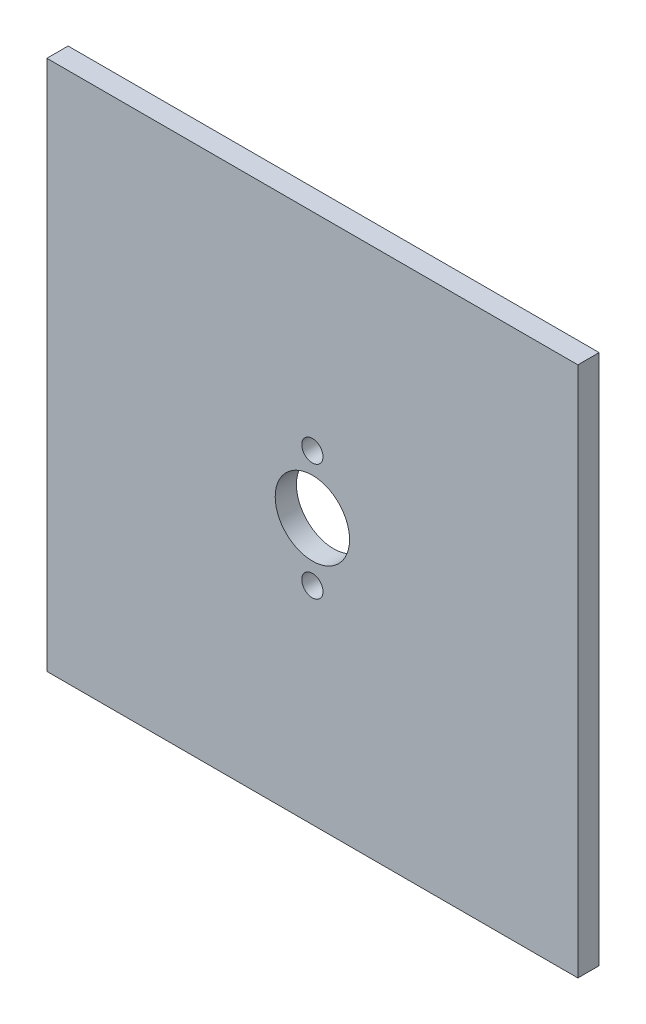
SolidWorks part; units mm, degrees
ref_plane "Front Plane" through (0, 0, 0) normal (0, 0, 1) x (1, 0, 0)
ref_plane "Top Plane" through (0, 0, 0) normal (0, 1, 0) x (1, 0, 0)
ref_plane "Right Plane" through (0, 0, 0) normal (1, 0, 0) x (0, 0, -1)
sketch "Sketch4" plane through (0, 0, 0) normal (0, 0, 1) x (1, 0, 0)
  line L1 (0, 0) -> (-50, 0)
  line L2 (0, 0) -> (0, 50)
  line L3 (0, 50) -> (-50, 50)
  line L4 (-50, 0) -> (-50, 50)
  dimension "D1" = 50
  dimension "D2" = 50
extrude "Boss-Extrude2" add sketch "Sketch4" along normal blind 2
sketch "Sketch5" plane through (0, 0, 2) normal (0, 0, 1) x (1, 0, 0)
  line L0 (-25, 50) -> (-25, 0) construction
  line L1 (0, 50) -> (-50, 50) construction
  line L2 (-50, 0) -> (0, 0) construction
  line L3 (-50, 25) -> (0, 25) construction
  line L4 (-50, 50) -> (-50, 0) construction
  line L5 (0, 0) -> (0, 50) construction
  circle A0 centre (-25, 30.5) radius 1
  circle A1 centre (-25, 19.5) radius 1
  dimension "D1" = 2
  dimension "D2" = 2
  dimension "D3" = 11
  dimension "D4" = 5.5
extrude "Cut-Extrude1" cut sketch "Sketch5" against normal up to next
sketch "Sketch6" plane through (0, 0, 0) normal (0, 0, -1) x (-1, 0, 0)
  line L0 (25, 50) -> (25, 0) construction
  line L1 (0, 50) -> (50, 50) construction
  line L2 (50, 0) -> (0, 0) construction
  line L3 (0, 25) -> (50, 25) construction
  line L4 (0, 0) -> (0, 50) construction
  line L5 (50, 50) -> (50, 0) construction
  circle A0 centre (25, 25) radius 3.5
  dimension "D1" = 7
extrude "Cut-Extrude2" cut sketch "Sketch6" against normal up to next
